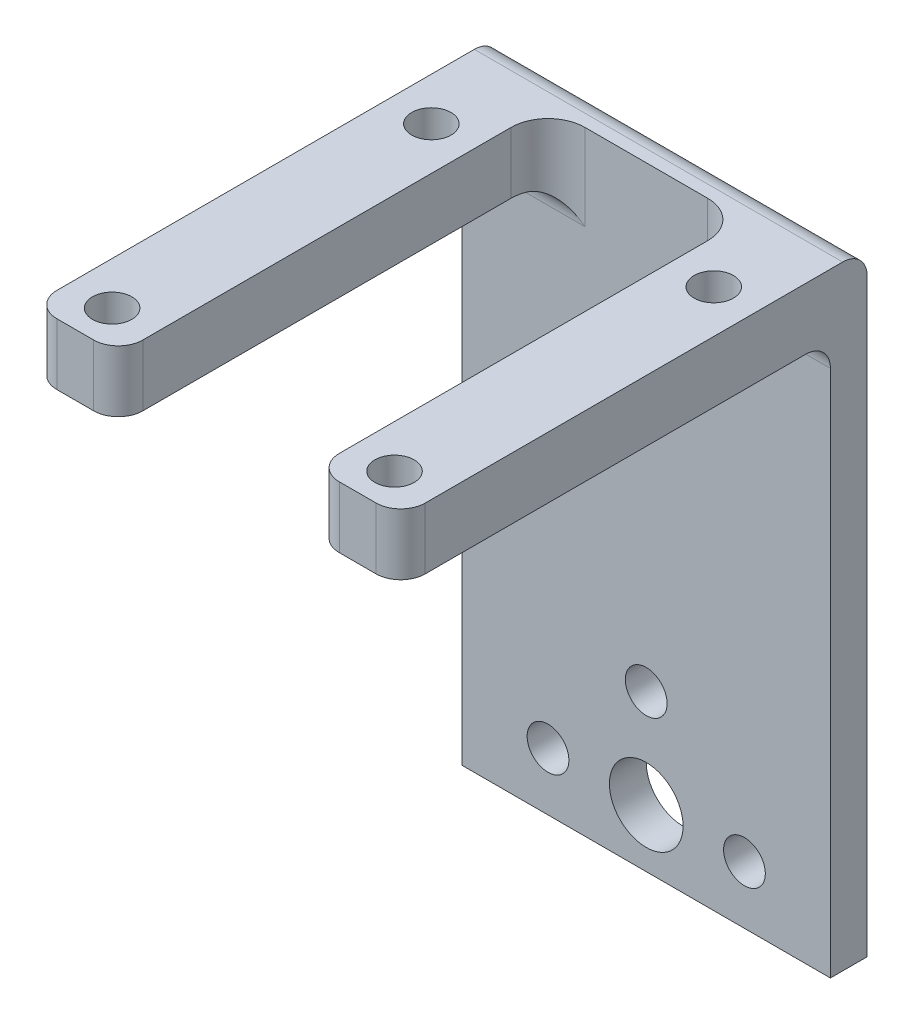
SolidWorks part; units mm, degrees
ref_plane "前视基准面" through (0, 0, 0) normal (0, 0, 1) x (1, 0, 0)
ref_plane "上视基准面" through (0, 0, 0) normal (0, 1, 0) x (1, 0, 0)
ref_plane "右视基准面" through (0, 0, 0) normal (1, 0, 0) x (0, 0, -1)
sketch "草图1" plane through (0, 0, 0) normal (0, 0, 1) x (1, 0, 0)
  line L0 (0, 148.5) -> (0, -94.9538) construction
  line L1 (105, -148.5) -> (-105, -148.5) construction
  line L2 (105, -148.5) -> (105, 148.5) construction
  line L3 (105, 148.5) -> (-105, 148.5) construction
  line L4 (-105, -148.5) -> (-105, 148.5) construction
  line L5 (105, -148.5) -> (-105, 148.5) construction
  line L6 (105, 148.5) -> (-105, -148.5) construction
  line L7 (35.8892, 121.6645) -> (-35.8892, 121.6645)
  line L8 (-35.8892, 121.6645) -> (-66.9017, 102.292)
  line L9 (-75, 40.9339) -> (-75, 31.2613)
  line L10 (-66.9017, 102.292) -> (-66.9017, 52.8701)
  line L11 (75, 40.9339) -> (75, 31.2613)
  line L12 (66.9017, 102.292) -> (66.9017, 52.8701)
  line L13 (35.8892, 121.6645) -> (66.9017, 102.292)
  line L14 (-75, 31.2613) -> (75, 31.2613)
  line L15 (-60, -148.5) -> (-60, -91.8129)
  line L16 (-75, 23.94) -> (75, 23.94)
  line L17 (-75, 23.94) -> (-75, 10.5626)
  line L18 (-38.8455, -105.5906) -> (-66.4608, -113.7617)
  line L19 (-66.4608, -113.7617) -> (-70.1743, -102.7328)
  line L20 (75, 23.94) -> (75, 10.5626)
  line L21 (66.4608, -113.7617) -> (70.1743, -102.7328)
  line L22 (38.8455, -105.5906) -> (66.4608, -113.7617)
  line L23 (-105, 93.0519) -> (105, 93.0519)
  line L24 (-105, 63.0519) -> (105, 63.0519)
  line L25 (-105, -90.0629) -> (-70.5337, -90.0629)
  line L26 (-105, -60.0629) -> (-67.4027, -60.0629)
  line L27 (60, -148.5) -> (60, 148.5)
  line L28 (-60, -58.3129) -> (-45, -58.3129)
  line L29 (-60, -61.8129) -> (-45, -61.8129)
  line L30 (-36, -58.3129) -> (-21, -58.3129)
  line L31 (-36, -61.8129) -> (-21, -61.8129)
  line L32 (-60, -88.3129) -> (-45, -88.3129)
  line L33 (-60, -91.8129) -> (-45, -91.8129)
  line L34 (-36, -88.3129) -> (-21, -88.3129)
  line L35 (-36, -91.8129) -> (-21, -91.8129)
  line L36 (-60, -58.3129) -> (-60, 148.5)
  line L37 (-19.25, -90.0629) -> (105, -90.0629)
  line L38 (-19.25, -60.0629) -> (19.25, -60.0629)
  line L39 (-60, -88.3129) -> (-60, -61.8129)
  line L40 (21, -58.3129) -> (36, -58.3129)
  line L41 (45, -58.3129) -> (60, -58.3129)
  line L42 (60, -61.8129) -> (45, -61.8129)
  line L43 (36, -61.8129) -> (21, -61.8129)
  line L44 (21, -88.3129) -> (36, -88.3129)
  line L45 (21, -91.8129) -> (36, -91.8129)
  line L46 (45, -88.3129) -> (60, -88.3129)
  line L47 (45, -91.8129) -> (60, -91.8129)
  line L48 (37.75, -60.0629) -> (43.25, -60.0629)
  line L49 (58.25, -60.0629) -> (105, -60.0629)
  line L50 (-60, 94.8019) -> (-45, 94.8019)
  line L51 (-36, 94.8019) -> (-21, 94.8019)
  line L52 (-60, 91.3019) -> (-45, 91.3019)
  line L53 (-36, 91.3019) -> (-21, 91.3019)
  line L54 (-60, 64.8019) -> (-45, 64.8019)
  line L55 (-60, 61.3019) -> (-45, 61.3019)
  line L56 (-36, 64.8019) -> (-21, 64.8019)
  line L57 (-36, 61.3019) -> (-21, 61.3019)
  line L58 (21, 94.8019) -> (36, 94.8019)
  line L59 (21, 91.3019) -> (36, 91.3019)
  line L60 (45, 94.8019) -> (60, 94.8019)
  line L61 (45, 91.3019) -> (60, 91.3019)
  line L62 (21, 61.3019) -> (36, 61.3019)
  line L63 (21, 64.8019) -> (36, 64.8019)
  line L64 (45, 61.3019) -> (60, 61.3019)
  line L65 (45, 64.8019) -> (60, 64.8019)
  line L66 (-33.1709, -104.7687) -> (33.1709, -104.7687)
  line L67 (0, -104.7687) -> (0, -148.5) construction
  arc A0 (-75, 40.9339) -> (-66.9017, 52.8701) centre (-79.7474, 52.8701) ccw
  arc A1 (75, 40.9339) -> (66.9017, 52.8701) centre (79.7474, 52.8701) cw
  arc A3 (-60, -88.3129) -> (-60, -91.8129) centre (-60, -90.0629) ccw
  arc A4 (-60, -58.3129) -> (-60, -61.8129) centre (-60, -60.0629) ccw
  circle A5 centre (-60, 63.0519) radius 1.75
  circle A6 centre (-60, 93.0519) radius 1.75
  circle A7 centre (60, 93.0519) radius 1.75
  circle A8 centre (60, 63.0519) radius 1.75
  arc A9 (60, -91.8129) -> (60, -88.3129) centre (60, -90.0629) ccw
  arc A10 (60, -61.8129) -> (60, -58.3129) centre (60, -60.0629) ccw
  arc A11 (-36, -58.3129) -> (-36, -61.8129) centre (-36, -60.0629) ccw
  arc A12 (-36, -88.3129) -> (-36, -91.8129) centre (-36, -90.0629) ccw
  arc A13 (36, -61.8129) -> (36, -58.3129) centre (36, -60.0629) ccw
  arc A14 (36, -91.8129) -> (36, -88.3129) centre (36, -90.0629) ccw
  arc A15 (-45, -61.8129) -> (-45, -58.3129) centre (-45, -60.0629) ccw
  arc A16 (-21, -61.8129) -> (-21, -58.3129) centre (-21, -60.0629) ccw
  arc A17 (-45, -91.8129) -> (-45, -88.3129) centre (-45, -90.0629) ccw
  arc A18 (-21, -91.8129) -> (-21, -88.3129) centre (-21, -90.0629) ccw
  arc A19 (45, -58.3129) -> (45, -61.8129) centre (45, -60.0629) ccw
  arc A20 (21, -58.3129) -> (21, -61.8129) centre (21, -60.0629) ccw
  arc A21 (21, -88.3129) -> (21, -91.8129) centre (21, -90.0629) ccw
  arc A22 (45, -88.3129) -> (45, -91.8129) centre (45, -90.0629) ccw
  circle A23 centre (-36, 93.0519) radius 1.75
  circle A24 centre (-36, 63.0519) radius 1.75
  circle A25 centre (36, 93.0519) radius 1.75
  circle A26 centre (36, 63.0519) radius 1.75
  circle A27 centre (-45, 93.0519) radius 1.75
  circle A28 centre (-21, 93.0519) radius 1.75
  circle A29 centre (-45, 63.0519) radius 1.75
  circle A30 centre (-21, 63.0519) radius 1.75
  circle A31 centre (21, 93.0519) radius 1.75
  circle A32 centre (21, 63.0519) radius 1.75
  circle A33 centre (45, 93.0519) radius 1.75
  circle A34 centre (45, 63.0519) radius 1.75
  arc A35 (33.1709, -104.7687) -> (38.8455, -105.5906) centre (33.1709, -124.7687) cw
  arc A36 (-33.1709, -104.7687) -> (-38.8455, -105.5906) centre (-33.1709, -124.7687) ccw
  spline S0 degree 3 poles (-75, 10.5626) (-72.6959, 1.9073) (-70.3396, -13.3728) (-67.1028, -43.6255) (-66.7657, -72.9327) (-71.8903, -95.1489) (-70.1743, -102.7328) knots 0 0 0 0 0.235247 0.406294 0.801186 1 1 1 1
  spline S1 degree 3 poles (75, 10.5626) (72.6959, 1.9073) (70.3396, -13.3728) (67.1028, -43.6255) (66.7657, -72.9327) (71.8903, -95.1489) (70.1743, -102.7328) knots 0 0 0 0 0.235247 0.406294 0.801186 1 1 1 1
  point P0 (0, 0)
  point P27 (0, 121.6645)
  point P42 (0, -94.0966)
  dimension "D1" = 60
  dimension "D4" = 20
  dimension "D5" = 24
  dimension "D7" = 24
  dimension "D9" = 15
  dimension "D10" = 15
  dimension "D13" = 24
  dimension "D17" = 15
  dimension "D2" = 30
  dimension "D3" = 30
  dimension "D6" = 24
  dimension "D8" = 24
  dimension "D11" = 15
  dimension "D12" = 15
  dimension "D14" = 24
  dimension "D15" = 24
  dimension "D16" = 24
  dimension "D18" = 15
  dimension "D19" = 15
  dimension "D20" = 15
  dimension "D21" = 15
  dimension "D22" = 15
  dimension "D23" = 15
  dimension "D24" = 15
  dimension "D25" = 15
  dimension "D26" = 15
  dimension "D27" = 15
  dimension "D28" = 15
  dimension "D29" = 3.5
  dimension "D30" = 3.5
  dimension "D31" = 3.5
extrude "凸台-拉伸1" add sketch "草图1" along normal blind 3 contours A34 L24 A26 L62 A32 A30 L57 A24 A29 L55 L36 L14 L27 L64 | A5 L24 L10 A0 L9 L14 L36 | A6 L23 L10 L24 A5 L36 | A6 L36 L8 L10 L23 | A33 L60 L27 L13 L7 L8 L36 L50 A27 L23 A23 L51 A28 A31 L58 A25 | A34 L65 L27 L61 A33 L23 A25 L59 A31 A28 L53 A23 A27 L52 L36 L54 A29 L24 A24 L56 A30 A32 L63 A26 | A7 L23 L12 L13 L27 | A8 L24 L12 L23 A7 L27 | A8 L27 L14 L11 A1 L12 L24 | A22 L46 L27 L42 A19 A13 L43 A20 A16 L31 A11 L30 L40 L41 L16 L36 L28 A15 L29 L39 L32 A17 L33 L15 L18 L22 L47 A14 L45 A21 A18 L35 A12 L34 | L17 S0 L19 L18 L15 A3 L39 A4 L36 L16 | S1 L20 L16 L27 A10 L49 | S1 L49 A10 L27 A9 L37 | S1 L37 A9 L27 L22 L21 region at (0, 106.7597, 0) region at (63.3118, 98.9762, 0) region at (-63.3118, 98.9762, 0) region at (63.5153, 78.0519, 0) region at (-63.5153, 78.0519, 0) region at (65.7633, 44.067, 0) region at (0, 78.0519, 0) region at (-65.7633, 44.067, 0) region at (0, 46.6707, 0) region at (0, -40.0712, 0) region at (65.6849, -11.6712, 0) region at (-65.3451, -38.0027, 0) region at (64.4303, -76.0355, 0) region at (65.0264, -100.7629, 0)
sketch "草图7" plane through (0, 0, 0) normal (0, 0, -1) x (-1, 0, 0)
  line L0 (0, 121.6645) -> (0, -104.7687) construction
  line L1 (-35.8892, 121.6645) -> (35.8892, 121.6645) construction
  line L2 (33.1709, -104.7687) -> (-33.1709, -104.7687) construction
  line L3 (0, 41.2613) -> (-21, 41.2613) construction
  line L4 (0, 41.2613) -> (21, 41.2613) construction
  line L5 (0, 13.94) -> (-21, 13.94) construction
  line L6 (0, 13.94) -> (21, 13.94) construction
  line L7 (75, 23.94) -> (-75, 23.94) construction
  line L8 (75, 31.2613) -> (-75, 31.2613) construction
  circle A0 centre (-21, 41.2613) radius 2.25
  circle A1 centre (21, 41.2613) radius 2.25
  circle A2 centre (-21, 13.94) radius 2.25
  circle A3 centre (21, 13.94) radius 2.25
  dimension "D1" = 10
  dimension "D2" = 10
extrude "切除-拉伸2" cut sketch "草图7" against normal through all
sketch "草图8" plane through (0, 0, 3) normal (0, 0, 1) x (1, 0, 0)
  line L0 (0, 121.6645) -> (0, -1.9696) construction
  line L1 (35.8892, 121.6645) -> (-35.8892, 121.6645) construction
  line L2 (-33.1709, -104.7687) -> (33.1709, -104.7687) construction
  line L3 (-33.409, 20.409) -> (-12.6214, -0.3786)
  line L4 (31.818, -51.182) -> (-31.818, -51.182)
  line L5 (35, -48) -> (35, 15.6418)
  line L8 (-35, 18.818) -> (-12.6214, -3.5605) construction
  line L9 (-33.409, -52.773) -> (-12.5737, -31.9377)
  line L10 (-36.591, 17.227) -> (-15.8034, -3.5605)
  line L11 (33.4105, 20.4105) -> (12.573, -0.427)
  line L12 (15.803, -3.5609) -> (36.5881, 17.2241)
  line L13 (31.8195, 18.8195) -> (-31.818, 18.818)
  line L14 (-15.8038, -28.8038) -> (-36.591, -49.591)
  line L15 (12.5534, -31.9174) -> (33.409, -52.773)
  line L16 (34.9993, 18.8173) -> (12.6207, -3.5613) construction
  line L17 (0, -30.3951) -> (0, -104.7687) construction
  line L18 (-35, -48) -> (-35, 15.636)
  line L19 (-11.9624, -1.9696) -> (-14.2124, -1.9696) construction
  line L20 (15.8034, -28.8034) -> (36.591, -49.591)
  line L21 (14.2117, -30.3951) -> (11.9607, -30.3951) construction
  line L22 (14.2117, -30.3951) -> (14.2117, -28.1441) construction
  line L23 (14.2117, -1.9696) -> (11.9612, -1.9696) construction
  line L24 (-14.2124, -30.3951) -> (-14.2124, -28.1446) construction
  line L25 (14.2117, -30.3951) -> (12.62, -28.8034) construction
  line L26 (14.2117, -1.9696) -> (12.6204, -3.5609) construction
  line L27 (12.6207, -28.8027) -> (35, -51.182) construction
  line L28 (-12.6215, -3.5606) -> (-14.2124, -1.9696) construction
  line L29 (-14.2124, -4.2196) -> (-14.2124, -1.9696) construction
  line L30 (-12.6214, -28.8034) -> (-35, -51.182) construction
  line L31 (-12.6211, -28.8037) -> (-14.2124, -30.3951) construction
  line L32 (-11.9619, -30.3951) -> (-14.2124, -30.3951) construction
  line L33 (14.2117, -4.2201) -> (14.2117, -1.9696) construction
  line L34 (11.0312, -30.3951) -> (0, -30.3951) construction
  arc A0 (-33.409, 20.409) -> (-36.591, 17.227) centre (-35, 18.818) ccw
  arc A1 (36.5881, 17.2241) -> (33.4105, 20.4105) centre (34.9993, 18.8173) ccw
  arc A2 (-36.591, -49.591) -> (-33.409, -52.773) centre (-35, -51.182) ccw
  arc A3 (33.409, -52.773) -> (36.591, -49.591) centre (35, -51.182) ccw
  arc A4 (-15.8034, -3.5605) -> (-12.6214, -0.3786) centre (-14.2124, -1.9696) ccw
  arc A5 (12.6692, -0.3308) -> (15.803, -3.5609) centre (14.2117, -1.9696) ccw
  arc A6 (-12.6699, -32.0338) -> (-15.8038, -28.8038) centre (-14.2124, -30.3951) ccw
  arc A7 (15.8034, -28.8034) -> (12.6894, -32.0534) centre (14.2117, -30.3951) ccw
  circle A8 centre (-0.0004, -16.1823) radius 8
  point P6 (0, -16.182)
  point P13 (-0.0004, -16.1823)
extrude "切除-拉伸3" cut sketch "草图8" against normal through all contours L10 A4 L3 A0 | L11 A5 L12 A1 | L20 A7 L15 A3 | L9 A6 L14 A2 | A8 region at (-24.6062, 8.4242, 3) region at (24.6054, 8.4234, 3) region at (-24.6061, -40.7881, 3) region at (24.6056, -40.7877, 3) region at (-0.0004, -16.1823, 3)
sketch "草图9" plane through (0, 0, 3) normal (0, 0, 1) x (1, 0, 0)
  line L0 (-70.7828, -98.747) -> (70.7828, -98.747) construction
  line L1 (0, -98.747) -> (0, -104.7687) construction
  line L2 (55, -100.497) -> (20, -100.497)
  line L3 (-55, -96.997) -> (-20, -96.997)
  line L4 (-55, -100.497) -> (-20, -100.497)
  line L5 (-33.1709, -104.7687) -> (33.1709, -104.7687) construction
  line L6 (55, -96.997) -> (20, -96.997)
  arc A0 (-55, -96.997) -> (-55, -100.497) centre (-55, -98.747) ccw
  arc A1 (-20, -100.497) -> (-20, -96.997) centre (-20, -98.747) ccw
  arc A2 (20, -100.497) -> (20, -96.997) centre (20, -98.747) cw
  arc A3 (55, -96.997) -> (55, -100.497) centre (55, -98.747) cw
  spline S0 degree 3 poles (-75, 10.5626) (-72.6959, 1.9073) (-70.3396, -13.3728) (-67.1028, -43.6255) (-66.7657, -72.9327) (-71.8903, -95.1489) (-70.1743, -102.7328) knots 0 0 0 0 0.235247 0.406294 0.801186 1 1 1 1 construction
  spline S1 degree 3 poles (75, 10.5626) (72.6959, 1.9073) (70.3396, -13.3728) (67.1028, -43.6255) (66.7657, -72.9327) (71.8903, -95.1489) (70.1743, -102.7328) knots 0 0 0 0 0.235247 0.406294 0.801186 1 1 1 1 construction
  dimension "D1" = 35
  dimension "D2" = 20
extrude "切除-拉伸4" cut sketch "草图9" against normal blind 3
sketch "草图10" plane through (0, 0, 3) normal (0, 0, 1) x (1, 0, 0)
  line L0 (-21, -60.0629) -> (-21, -90.0629) construction
  line L1 (21, -60.0629) -> (21, -90.0629) construction
  line L2 (-21, -75.0629) -> (-17.5, -75.0629) construction
  line L4 (12.5, -80.0629) -> (-12.5, -80.0629)
  line L6 (12.5, -70.0629) -> (-12.5, -70.0629)
  line L11 (17.5, -75.0629) -> (21, -75.0629) construction
  arc A0 (-12.5, -70.0629) -> (-12.5, -80.0629) centre (-12.5, -75.0629) ccw
  arc A1 (12.5, -80.0629) -> (12.5, -70.0629) centre (12.5, -75.0629) ccw
  point P11 (0, -75.0629)
extrude "切除-拉伸5" cut sketch "草图10" against normal blind 3
sketch "草图11" plane through (0, 0, 3) normal (0, 0, 1) x (1, 0, 0)
  line L0 (-21, 93.0519) -> (-21, 63.0519) construction
  line L1 (21, 93.0519) -> (21, 63.0519) construction
  line L2 (-21, 78.0519) -> (-20, 78.0519) construction
  line L4 (15, 73.0519) -> (-15, 73.0519)
  line L6 (15, 83.0519) -> (-15, 83.0519)
  line L10 (20, 78.0519) -> (21, 78.0519) construction
  arc A0 (-15, 83.0519) -> (-15, 73.0519) centre (-15, 78.0519) ccw
  arc A1 (15, 73.0519) -> (15, 83.0519) centre (15, 78.0519) ccw
  point P10 (0, 78.0519)
  dimension "D1" = 30
extrude "切除-拉伸8" cut sketch "草图11" against normal blind 3
sketch "草图12" plane through (0, 0, 3) normal (0, 0, 1) x (1, 0, 0)
  line L0 (0, 121.6645) -> (0, 83.0519) construction
  line L1 (35.8892, 121.6645) -> (-35.8892, 121.6645) construction
  line L2 (15, 83.0519) -> (-15, 83.0519) construction
  circle A0 centre (0, 106.3718) radius 11 construction
  circle A1 centre (0, 106.3718) radius 8 construction
  circle A2 centre (0, 114.3718) radius 1.7
  circle A3 centre (0, 98.3718) radius 1.7
  circle A4 centre (8, 106.3718) radius 1.7
  circle A5 centre (-8, 106.3718) radius 1.7
extrude "切除-拉伸9" cut sketch "草图12" against normal blind 3
sketch "草图13" plane through (0, 0, 3) normal (0, 0, 1) x (1, 0, 0)
  line L0 (0, -104.7687) -> (0, -80.0629) construction
  line L1 (-33.1709, -104.7687) -> (33.1709, -104.7687) construction
  line L2 (-12.5, -80.0629) -> (12.5, -80.0629) construction
  circle A0 centre (0, -92.4158) radius 8 construction
  circle A1 centre (0, -84.4158) radius 1.7
  circle A2 centre (8, -92.4158) radius 1.7
  circle A3 centre (0, -100.4158) radius 1.7
  circle A4 centre (-8, -92.4158) radius 1.7
extrude "切除-拉伸11" cut sketch "草图13" against normal blind 3
sketch "草图14" plane through (0, 0, 3) normal (0, 0, 1) x (1, 0, 0)
  line L0 (0, 23.94) -> (0, -104.7687) construction
  line L1 (-55.4755, 8.9197) -> (-55.4755, -46.0803)
  line L2 (-58.9755, 8.9197) -> (-58.9755, -46.0803)
  line L3 (-75, 23.94) -> (75, 23.94) construction
  line L4 (-33.1709, -104.7687) -> (33.1709, -104.7687) construction
  line L5 (58.9755, 8.9197) -> (58.9755, -46.0803)
  line L6 (55.4755, 8.9197) -> (55.4755, -46.0803)
  arc A0 (-55.4755, 8.9197) -> (-58.9755, 8.9197) centre (-57.2255, 8.9197) ccw
  arc A1 (-58.9755, -46.0803) -> (-55.4755, -46.0803) centre (-57.2255, -46.0803) ccw
  arc A2 (58.9755, -46.0803) -> (55.4755, -46.0803) centre (57.2255, -46.0803) cw
  arc A3 (55.4755, 8.9197) -> (58.9755, 8.9197) centre (57.2255, 8.9197) cw
extrude "切除-拉伸12" cut sketch "草图14" against normal through all
fillet "圆角1" radius 2 2 edges at (75, 31.2613, 1.5) (-75, 31.2613, 1.5)
fillet "圆角2" radius 2 2 edges at (-75, 23.94, 1.5) (75, 23.94, 1.5)
sketch "草图15" plane through (0, 0, 0) normal (0, 0, -1) x (-1, 0, 0)
  line L0 (0, 121.6645) -> (0, 31.2613) construction
  line L1 (-35.8892, 121.6645) -> (35.8892, 121.6645) construction
  line L2 (73, 31.2613) -> (-73, 31.2613) construction
  line L3 (-27.5188, 121.6645) -> (-63.6963, 99.0657) construction
  line L4 (-35.8892, 121.6645) -> (-66.9017, 102.292) construction
  line L5 (-61.1842, 102.4035) -> (-34.7748, 118.9006)
  line L6 (-59.5948, 99.8591) -> (-33.1854, 116.3562)
  line L7 (27.5188, 121.6645) -> (63.6963, 99.0657) construction
  line L8 (59.5948, 99.8591) -> (33.1854, 116.3562)
  line L9 (61.1842, 102.4035) -> (34.7748, 118.9006)
  arc A0 (-61.1842, 102.4035) -> (-59.5948, 99.8591) centre (-60.3895, 101.1313) ccw
  arc A1 (-33.1854, 116.3562) -> (-34.7748, 118.9006) centre (-33.9801, 117.6284) ccw
  arc A2 (33.1854, 116.3562) -> (34.7748, 118.9006) centre (33.9801, 117.6284) cw
  arc A3 (61.1842, 102.4035) -> (59.5948, 99.8591) centre (60.3895, 101.1313) cw
extrude "切除-拉伸13" cut sketch "草图15" against normal through all
sketch "草图16" plane through (0, 0, 0) normal (0, 0, -1) x (-1, 0, 0)
  line L0 (0, 121.6645) -> (0, 31.2613) construction
  line L1 (-35.8892, 121.6645) -> (35.8892, 121.6645) construction
  line L2 (73, 31.2613) -> (-73, 31.2613) construction
  line L3 (-21, 41.2613) -> (-66.71, 41.2613) construction
  line L4 (-61.517, 42.7613) -> (-32.0563, 42.7613)
  line L5 (-61.517, 39.7613) -> (-32.0563, 39.7613)
  line L6 (21, 41.2613) -> (66.71, 41.2613) construction
  line L7 (61.517, 39.7613) -> (32.0563, 39.7613)
  line L8 (61.517, 42.7613) -> (32.0563, 42.7613)
  arc A0 (-61.517, 42.7613) -> (-61.517, 39.7613) centre (-61.517, 41.2613) ccw
  arc A1 (-32.0563, 39.7613) -> (-32.0563, 42.7613) centre (-32.0563, 41.2613) ccw
  arc A2 (32.0563, 39.7613) -> (32.0563, 42.7613) centre (32.0563, 41.2613) cw
  arc A3 (61.517, 42.7613) -> (61.517, 39.7613) centre (61.517, 41.2613) cw
extrude "切除-拉伸14" cut sketch "草图16" against normal through all
sketch "草图17" plane through (0, 0, 0) normal (0, 0, -1) x (-1, 0, 0)
  text T0 "Y" font "黑体" height in points 72
extrude "切除-拉伸15" cut sketch "草图17" against normal through all
sketch "草图18" plane through (0, 0, 0) normal (0, 0, -1) x (-1, 0, 0)
  text T0 "H" font "黑体" height in points 72
extrude "切除-拉伸16" cut sketch "草图18" against normal through all
sketch "草图19" plane through (0, 0, 3) normal (0, 0, 1) x (1, 0, 0)
  line L2 (34.7748, 118.9006) -> (61.1842, 102.4035) construction
  line L3 (59.5948, 99.8591) -> (33.1854, 116.3562) construction
  line L6 (42.8907, 113.8308) -> (53.0682, 107.4733)
  line L7 (51.4789, 104.9289) -> (41.3014, 111.2864)
  line L8 (53.5457, 105.4064) -> (40.8239, 113.3533) construction
  line L10 (50.4193, 103.2326) -> (40.2418, 109.5902)
  line L11 (47.1848, 109.3799) -> (58.1535, 126.9392) construction
  line L12 (55.242, 104.3468) -> (61.9502, 115.0858)
  line L13 (39.1276, 114.4129) -> (45.8359, 125.1519)
  line L14 (61.9502, 115.0858) -> (45.8359, 125.1519)
  line L15 (35.8892, 121.6645) -> (66.9017, 102.292) construction
  arc A8 (51.4789, 104.9289) -> (53.0682, 107.4733) centre (52.2735, 106.2011) ccw
  arc A9 (42.8907, 113.8308) -> (41.3014, 111.2864) centre (42.096, 112.5586) ccw
  arc A10 (50.4193, 103.2326) -> (55.242, 104.3468) centre (52.2735, 106.2011) ccw
  arc A11 (39.1276, 114.4129) -> (40.2418, 109.5902) centre (42.096, 112.5586) ccw
  point P16 (47.1848, 109.3799)
  dimension "D3" = 8.2274
  dimension "D1" = 6
  dimension "D2" = 6
extrude "凸台-拉伸2" add sketch "草图19" along normal blind 3
sketch "草图20" plane through (0, 0, 6) normal (0, 0, 1) x (1, 0, 0)
  line L0 (45.3305, 106.4114) -> (53.8931, 120.1188) construction
  line L1 (40.2418, 109.5902) -> (50.4193, 103.2326) construction
  line L2 (61.9502, 115.0858) -> (45.8359, 125.1519) construction
  line L3 (61.9502, 115.0858) -> (45.8359, 125.1519)
  line L4 (60.3609, 112.5414) -> (44.2465, 122.6075)
  line L5 (45.8359, 125.1519) -> (44.2465, 122.6075)
  line L6 (60.3609, 112.5414) -> (61.9502, 115.0858)
  dimension "D1" = 3
extrude "凸台-拉伸3" add sketch "草图20" along normal blind 15
mirror "镜向1" about plane through (0, 0, 0) normal (1, 0, 0) of bodies 127
sketch "草图21" plane through (0, 121.6645, 0) normal (0, 1, 0) x (1, 0, 0)
  line L1 (-66.9017, -3) -> (64.5469, -3)
  line L2 (-66.9017, -3) -> (-66.9017, -35.9294)
  line L3 (-66.9017, -35.9294) -> (64.5469, -35.9294)
  line L4 (64.5469, -3) -> (64.5469, -35.9294)
extrude "切除-拉伸17" cut sketch "草图21" against normal blind 65 and the other way blind 45
ref_plane "基准面1" through (0, 0, 13) normal (0, 0, 1) x (1, 0, 0)
sketch "草图22" plane through (0, 0, 13) normal (0, 0, 1) x (1, 0, 0)
  line L0 (-8, 106.3718) -> (8, 106.3718) construction
  line L1 (-10.583, 101.3718) -> (10.583, 101.3718)
  line L2 (0, 101.3718) -> (0, 116.0718) construction
  line L3 (35.8892, 121.6645) -> (-35.8892, 121.6645) construction
  line L4 (-15, 151.6645) -> (15, 151.6645)
  line L6 (-15, 151.6645) -> (-15, 101.6645)
  line L7 (-15, 101.6645) -> (15, 101.6645)
  line L8 (15, 151.6645) -> (15, 101.6645)
  line L10 (-15, 101.6645) -> (-13.6906, 103.7166) construction
  circle A0 centre (0, 114.3718) radius 1.7 construction
  circle A1 centre (8, 106.3718) radius 1.7 construction
  circle A2 centre (-8, 106.3718) radius 1.7 construction
  circle A3 centre (0, 114.3718) radius 1.7
  circle A4 centre (8, 106.3718) radius 1.7
  circle A5 centre (-8, 106.3718) radius 1.7
  circle A7 centre (0, 106.3718) radius 3
  point P18 (0, 0)
  point P20 (0, 0)
  point P21 (-1.0292, 123.5594)
  point P23 (14.6782, 127.1092)
  point P25 (15.0458, 144.8331)
  point P26 (0, 0)
  point P27 (0, 0)
  dimension "D1" = 5
  dimension "D2" = 50
  dimension "D3" = 30
  dimension "D4" = 15
  dimension "D5" = 20
extrude "凸台-拉伸4" add sketch "草图22" along normal blind 3 separate body contours L8 L4 L6 L7 L1 A7 A5 A4 A3 region at (0, 127.3941, 13)
fillet "圆角3" [suppressed] radius 5
sketch "草图23" plane through (0, 0, 16) normal (0, 0, 1) x (1, 0, 0)
  line L0 (15, 151.6645) -> (15, 101.6645) construction
  line L1 (-15, 151.6645) -> (15, 151.6645)
  line L2 (-15, 151.6645) -> (-15, 146.6645)
  line L3 (-15, 146.6645) -> (15, 146.6645)
  line L4 (15, 151.6645) -> (15, 146.6645)
  line L5 (15, 151.6645) -> (15, 101.6645) construction
  point P7 (15, 137.1299)
  dimension "D1" = 5
extrude "凸台-拉伸5" add sketch "草图23" along normal blind 35
sketch "草图25" plane through (0, 146.6645, 0) normal (0, -1, 0) x (1, 0, 0)
  line L0 (0, 16) -> (0, 51) construction
  line L2 (-15, 51) -> (15, 51) construction
  line L3 (-15, 51) -> (-15, 16) construction
  line L4 (8, 51) -> (-8, 51)
  line L5 (8, 51) -> (8, 16)
  line L6 (8, 16) -> (-8, 16)
  line L7 (-8, 51) -> (-8, 16)
  line L8 (8, 51) -> (-8, 16) construction
  line L9 (8, 16) -> (-8, 51) construction
  line L10 (-15, 13) -> (15, 13) construction
  point P2 (0, 0)
  point P3 (0, 0)
  point P6 (0, 33.5)
  dimension "D1" = 7
  dimension "D2" = 3
extrude "切除-拉伸18" cut sketch "草图25" against normal blind 35
fillet "圆角4" radius 3 2 edges at (-8, 149.1645, 16) (8, 149.1645, 16)
ref_plane "基准面2" through (0, 161.6645, 0) normal (0, 1, 0) x (1, 0, 0)
sketch "草图26" plane through (0, 161.6645, 0) normal (0, 1, 0) x (1, 0, 0)
  line L0 (0, 0) -> (0, -105.0488) construction
  line L1 (-8, -51) -> (-15, -51) construction
  line L2 (27.5, -51) -> (-27.5, -51)
  line L3 (27.5, -51) -> (27.5, -19)
  line L4 (27.5, -19) -> (-27.5, -19)
  line L5 (-27.5, -51) -> (-27.5, -19)
  line L6 (27.5, -51) -> (-27.5, -19) construction
  line L7 (27.5, -19) -> (-27.5, -51) construction
  line L8 (-27.5, -35) -> (27.5, -35) construction
  line L9 (0, -48.1253) -> (-21.2, -48.1253) construction
  line L10 (-21.2, -48.1253) -> (-21.2, -19) construction
  circle A1 centre (-12.95, -35) radius 8.25
  circle A2 centre (12.95, -35) radius 8.25
  point P3 (0, -35)
  dimension "D1" = 16.5
extrude "凸台-拉伸6" add sketch "草图26" along normal blind 3 separate body
sketch "草图27" plane through (0, 164.6645, 0) normal (0, 1, 0) x (1, 0, 0)
  line L0 (-15, -51) -> (-15, -13) construction
  line L1 (-49.7217, -13) -> (49.7217, -13) construction
  line L2 (-15, -51) -> (-15, -13) construction
  line L3 (-8, -51) -> (-8, -19) construction
  line L4 (0, -51) -> (0, -19) construction
  line L5 (-27.5, -51) -> (27.5, -51) construction
  line L6 (27.5, -19) -> (-27.5, -19) construction
  line L7 (-8, -19) -> (-15, -19) construction
  line L8 (-11.5, -19) -> (-11.5, -51) construction
  line L9 (-12.95, -35) -> (12.95, -35) construction
  circle A0 centre (-11.5, -22) radius 1.6
  circle A1 centre (-11.5, -48) radius 1.6
  circle A2 centre (11.5, -48) radius 1.6
  circle A3 centre (11.5, -22) radius 1.6
  dimension "D1" = 3
extrude "切除-拉伸19" cut sketch "草图27" against normal through all
sketch "草图29" plane through (0, 0, 19) normal (0, 0, -1) x (-1, 0, 0)
  line L0 (35.8892, 121.6645) -> (66.9017, 102.292) construction
  line L1 (-35.8892, 121.6645) -> (-66.9017, 102.292) construction
  line L2 (35.8892, 121.6645) -> (66.9017, 102.292)
  line L3 (-35.8892, 121.6645) -> (-66.9017, 102.292)
  line L4 (-27.5, 164.6645) -> (-79.9352, 131.91)
  line L5 (-27.5, 161.6645) -> (-79.9352, 128.91)
  line L6 (20.9, 161.6645) -> (-20.9, 161.6645) construction
  line L7 (27.5, 164.6645) -> (79.9352, 131.91)
  line L8 (27.5, 161.6645) -> (79.9352, 128.91)
  line L9 (79.9352, 128.91) -> (79.9352, 131.91)
  line L10 (0, 164.6645) -> (0, -104.7687) construction
  line L11 (-27.5, 164.6645) -> (27.5, 164.6645) construction
  line L12 (33.1709, -104.7687) -> (-33.1709, -104.7687) construction
  line L13 (-79.9352, 128.91) -> (-79.9352, 131.91)
  line L14 (27.5, 161.6645) -> (27.5, 164.6645)
  line L15 (-27.5, 161.6645) -> (-27.5, 164.6645)
  line M11 (27.5, 161.6645) -> (27.5, 164.6645)
  line M13 (-27.5, 164.6645) -> (-27.5, 161.6645)
extrude "凸台-拉伸7" add sketch "草图29" against normal up to surface (32 mm away) contours L8 L9 L7 M11 | L13 L5 L4 M13 region at (53.7176, 146.7873, 19) region at (-53.7176, 146.7873, 19) up to face at (0, 163.1645, 51)
sketch "草图31" plane through (-81.708, 130.8026, 0) normal (-0.5298, 0.8481, 0) x (0.8481, 0.5298, 0)
  line L0 (2.0902, -35) -> (63.915, -35) construction
  line L1 (2.0902, -51) -> (2.0902, -19) construction
  line L2 (63.915, -19) -> (63.915, -51) construction
  line L3 (33.0026, -19) -> (33.0026, -51) construction
  line L4 (63.915, -19) -> (2.0902, -19) construction
  line L5 (2.0902, -51) -> (63.915, -51) construction
  circle A0 centre (20.0526, -35) radius 8.25
  circle A1 centre (45.9526, -35) radius 8.25
  dimension "D1" = 16.5
  dimension "D2" = 16.5
  dimension "D3" = 12.95
  dimension "D4" = 12.95
extrude "切除-拉伸20" cut sketch "草图31" against normal blind 3
sketch "草图32" plane through (0, 164.6645, 0) normal (0, 1, 0) x (1, 0, 0)
  line L0 (27.5, -19) -> (-27.5, -19) construction
  point P0 (0, -19)
mirror "镜向3" about plane through (0, 0, 0) normal (1, 0, 0) of "切除-拉伸20"
sketch "草图33" plane through (0, 164.6645, 0) normal (0, 1, 0) x (1, 0, 0)
  line L0 (0, -51) -> (0, 0) construction
  line L1 (-27.5, -51) -> (27.5, -51) construction
  line L2 (23, -14.5) -> (-23, -14.5)
  line L3 (27.5, -19) -> (-27.5, -19) construction
  line L4 (-23, -14.5) -> (-27.5, -19)
  line L5 (23, -14.5) -> (27.5, -19)
  line L6 (-27.5, -19) -> (27.5, -19)
  point P12 (0, -14.5)
  dimension "D1" = 4.5
extrude "凸台-拉伸8" add sketch "草图33" against normal up to surface (3 mm away) up to face at (-11.5, 161.6645, 23.6)
fillet "圆角5" radius 5 4 edges at (27.5, 163.1645, 19) (23, 163.1645, 14.5) (-23, 163.1645, 14.5) (-27.5, 163.1645, 19)
fillet "圆角6" radius 5 4 edges at (79.9352, 130.41, 51) (79.9352, 130.41, 19) (-79.9352, 130.41, 51) (-79.9352, 130.41, 19)
sketch "草图34" plane through (0, 164.6645, 0) normal (0, 1, 0) x (1, 0, 0)
  line L0 (0, 0) -> (0, -144.922) construction
  line L5 (27.5, -51) -> (27.5, -63) construction
  line L11 (-27.5, -57) -> (-18.9932, -65.7222)
  line L13 (-27.5, -51) -> (27.5, -51)
  line L14 (-27.5, -51) -> (-27.5, -57)
  line L16 (27.5, -51) -> (27.5, -57)
  line L17 (-18.9932, -65.7222) -> (-15.2908, -57)
  line L18 (-15.2908, -57) -> (-6.9612, -68.4118)
  line L19 (-6.9612, -68.4118) -> (0, -57)
  line L20 (6.9612, -68.4118) -> (0, -57)
  line L21 (15.2908, -57) -> (6.9612, -68.4118)
  line L22 (18.9932, -65.7222) -> (15.2908, -57)
  line L23 (27.5, -57) -> (18.9932, -65.7222)
extrude "凸台-拉伸10" add sketch "草图34" against normal up to surface (3 mm away) contours L19 L20 L21 L22 L23 L16 L13 L14 L11 L17 L18 up to face at (-11.5, 161.6645, 23.6)
sketch "草图35" plane through (0, 164.6645, 0) normal (0, 1, 0) x (1, 0, 0)
  line L0 (0, -14.5) -> (0, -32.5134) construction
  line L1 (20.9289, -14.5) -> (-20.9289, -14.5) construction
  line L2 (6.9612, -68.4118) -> (0, -57) construction
  line L3 (0, -48.7039) -> (0, -57) construction
  arc A0 (-4.4758, -50.9044) -> (4.4758, -50.9044) centre (0, -42.1087) ccw
  arc A1 (-4.4758, -46.9527) -> (4.4758, -46.9527) centre (0, -42.1087) ccw
  arc A2 (-4.4758, -50.9044) -> (-4.4758, -46.9527) centre (-3.6937, -48.9286) cw
  arc A3 (4.4758, -50.9044) -> (4.4758, -46.9527) centre (3.6937, -48.9286) ccw
extrude "切除-拉伸21" cut sketch "草图35" against normal blind 5
fillet "圆角7" radius 5 2 edges at (27.5, 163.1645, 51) (-27.5, 163.1645, 51)
fillet "圆角8" radius 2 2 edges at (-10, 146.6645, 16) (10, 146.6645, 16)
fillet "圆角9" radius 2 4 edges at (-15, 149.1645, 51) (-8, 149.1645, 51) (8, 149.1645, 51) (15, 149.1645, 51)
fillet "圆角10" radius 2 1 edges at (0, 151.6645, 13)
sketch "草图36" plane through (0, 121.6645, 0) normal (0, 1, 0) x (1, 0, 0)
  line L1 (-80.2063, 5.0081) -> (79.8299, 5.0081)
  line L2 (-80.2063, 5.0081) -> (-80.2063, -8.5767)
  line L3 (-80.2063, -8.5767) -> (79.8299, -8.5767)
  line L4 (79.8299, 5.0081) -> (79.8299, -8.5767)
extrude "切除-拉伸22" cut sketch "草图36" against normal through all
sketch "草图37" plane through (0, 0, 14.5) normal (0, 0, -1) x (-1, 0, 0)
  line L1 (105.1517, 101.6645) -> (30, 101.6645)
  line L2 (105.1517, 101.6645) -> (105.1517, 168.6645)
  line L3 (105.1517, 168.6645) -> (30, 168.6645)
  line L4 (30, 101.6645) -> (30, 168.6645)
  line L5 (-30, 101.6645) -> (-105.1517, 101.6645)
  line L6 (-30, 101.6645) -> (-30, 168.6645)
  line L7 (-30, 168.6645) -> (-105.1517, 168.6645)
  line L8 (-105.1517, 101.6645) -> (-105.1517, 168.6645)
  line L9 (30, 156.6645) -> (-30, 156.6645)
  line L10 (30, 156.6645) -> (30, 168.6645)
  line L11 (30, 168.6645) -> (-30, 168.6645)
  line L12 (-30, 156.6645) -> (-30, 168.6645)
  line L13 (15, 101.6645) -> (-15, 101.6645) construction
  line L14 (-15, 151.6645) -> (15, 151.6645) construction
  line L16 (-15, 149.6645) -> (-15, 101.6645) construction
  point P6 (27.6023, 163.5512)
  point P10 (30.3024, 152.9139)
  point P12 (38.9837, 165.4315)
  point P13 (40.4008, 146.6058)
  point P14 (27.8192, 150.6645)
  point P16 (80.7771, 163.0678)
  point P17 (-18.8472, 146.6207)
  point P18 (40.377, 163.1831)
  point P19 (-18.9565, 166.6796)
  point P20 (27.1507, 154.8827)
  point P21 (-25.3975, 145.1485)
  point P22 (26.1077, 155.5343)
  point P23 (0, 0)
  point P24 (33.8303, 162.7102)
  point P25 (65.7173, 105.6093)
  point P26 (30.0025, 153.1013)
  point P33 (105.1517, 101.6645)
  point P34 (80.1525, 162.6645)
  point P35 (33.9034, 150.6645)
  point P36 (33.9034, 151.5412)
  line M1 (20.9289, 164.6645) -> (-20.9289, 164.6645)
  line M2 (-20.9289, 164.6645) -> (-20.9289, 161.6645)
  line M3 (-20.9289, 161.6645) -> (20.9289, 161.6645)
  line M4 (20.9289, 161.6645) -> (20.9289, 164.6645)
  dimension "D1" = 60
  dimension "D2" = 12
  dimension "D3" = 5
  dimension "D4" = 15
extrude "切除-拉伸23" cut sketch "草图37" against normal through all contours L11 L10 L9 L4 L1 L2 L3 | L9 L4 L6 M3 | L4 L11 L6 M1 | L10 L11 L4 L9 M1 M4 M3 | L6 L4 M3 M1 | L9 L12 L11 L6 L7 L8 L5 | L12 L9 L6 L11 M3 M2 M1 region at (-67.5758, 135.1645, 14.5) region at (0, 157.2764, 14.5) region at (67.5758, 135.1645, 14.5) region at (0, 163.1645, 14.5)
